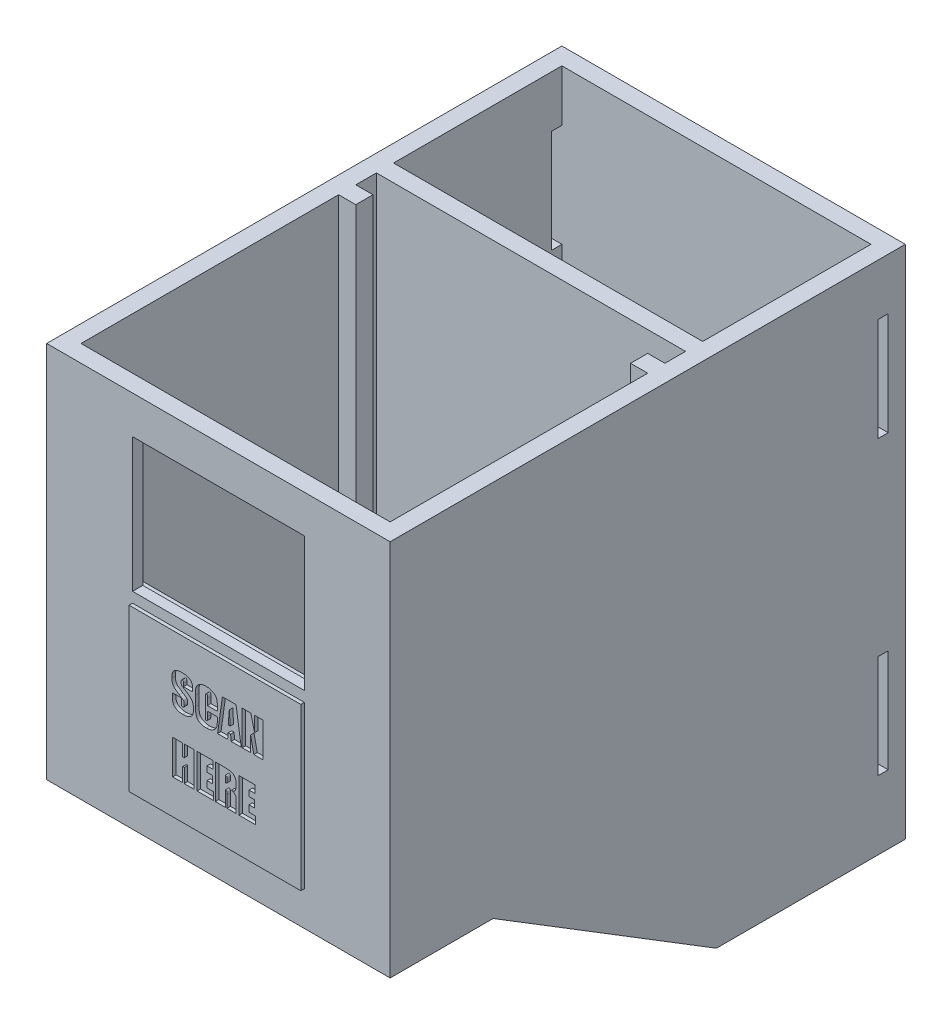
SolidWorks part; units mm, degrees
ref_plane "Front Plane" through (0, 0, 0) normal (0, 0, 1) x (1, 0, 0)
ref_plane "Top Plane" through (0, 0, 0) normal (0, 1, 0) x (1, 0, 0)
ref_plane "Right Plane" through (0, 0, 0) normal (1, 0, 0) x (0, 0, -1)
sketch "Sketch1" plane through (0, 0, 0) normal (0, 1, 0) x (1, 0, 0)
  line L1 (-50, -75) -> (50, -75)
  line L2 (-50, -75) -> (-50, 75)
  line L3 (-50, 75) -> (50, 75)
  line L4 (50, -75) -> (50, 75)
  line L5 (-50, -75) -> (50, 75) construction
  line L6 (-50, 75) -> (50, -75) construction
  point P0 (0, 0)
  dimension "D1" = 100
  dimension "D2" = 150
extrude "Boss-Extrude1" add sketch "Sketch1" along normal blind 150
sketch "Sketch13" plane through (50, 0, 0) normal (1, 0, 0) x (0, 0, -1)
  line L0 (-45, 40) -> (20, 0)
  line L1 (-75, 0) -> (-45, 0)
  line L2 (-75, 0) -> (-75, 40)
  line L3 (-75, 40) -> (-45, 40)
  line L5 (-75, 0) -> (75, 0) construction
  line L8 (-45, 0) -> (20, 0)
  dimension "D1" = 30
  dimension "D2" = 40
  dimension "D3" = 55
extrude "Cut-Extrude7" cut sketch "Sketch13" against normal up to next
shell "Shell1" thickness 5 removed face at (0, 150, 0)
sketch "Sketch3" plane through (0, 0, 0) normal (0, -1, 0) x (1, 0, 0)
  line L1 (50, 45) -> (50, 75) construction
  circle A0 centre (0, 60) radius 4
  circle A1 centre (-5, 50) radius 1.5
  circle A2 centre (5, 50) radius 1.5
  dimension "D3" = 8
  dimension "D4" = 3
  dimension "D5" = 10
  dimension "D7" = 10
  dimension "D8" = 5
  dimension "D1" = 60
  dimension "D2" = 50
extrude "Cut-Extrude2" cut sketch "Sketch3" against normal up to next
sketch "Sketch5" plane through (0, 0, 75) normal (0, 0, 1) x (1, 0, 0)
  line L0 (50, 150) -> (50, 40) construction
  line L1 (-25, 50) -> (25, 50)
  line L2 (-25, 50) -> (-25, 97)
  line L3 (-25, 97) -> (25, 97)
  line L4 (25, 50) -> (25, 97)
  line L5 (-25, 50) -> (25, 97) construction
  line L6 (-25, 97) -> (25, 50) construction
  line L7 (-50, 150) -> (50, 150) construction
  point P0 (0, 73.5)
  dimension "D1" = 50
  dimension "D2" = 47
  dimension "D3" = 50
  dimension "D4" = 76.5
extrude "Boss-Extrude3" add sketch "Sketch5" along normal blind 1
sketch "Sketch8" plane through (0, 0, 75) normal (0, 0, 1) x (1, 0, 0)
  line L0 (-50, 150) -> (-50, 40) construction
  line L1 (-25, 100) -> (25, 100)
  line L2 (-25, 100) -> (-25, 139)
  line L3 (-25, 139) -> (25, 139)
  line L4 (25, 100) -> (25, 139)
  line L5 (-25, 100) -> (25, 139) construction
  line L6 (-25, 139) -> (25, 100) construction
  line L7 (-50, 150) -> (50, 150) construction
  point P0 (0, 119.5)
  dimension "D1" = 50
  dimension "D2" = 39
  dimension "D3" = 50
  dimension "D4" = 50
extrude "Cut-Extrude3" cut sketch "Sketch8" against normal up to next
sketch "Sketch18" plane through (0, 0, 70) normal (0, 0, -1) x (-1, 0, 0)
  line L0 (-25, 139) -> (25, 139) construction
  line L1 (30, 99) -> (-26, 99)
  line L2 (30, 99) -> (30, 140)
  line L3 (30, 140) -> (-26, 140)
  line L4 (-26, 99) -> (-26, 140)
  line L6 (-25, 100) -> (-25, 139) construction
  line L7 (25, 139) -> (25, 100) construction
  dimension "D1" = 1
  dimension "D2" = 41
  dimension "D3" = 1
  dimension "D4" = 5
extrude "Cut-Extrude9" cut sketch "Sketch18" against normal blind 2
sketch "Sketch20" plane through (0, 0, 76) normal (0, 0, 1) x (1, 0, 0)
  line L0 (25, 97) -> (-25, 97) construction
  line L1 (-23, 96) -> (23, 96)
  line L2 (-23, 96) -> (-23, 51)
  line L3 (-23, 51) -> (23, 51)
  line L4 (23, 96) -> (23, 51)
  line L5 (-25, 50) -> (25, 50) construction
  line L6 (25, 50) -> (25, 97) construction
  line L7 (-25, 97) -> (-25, 50) construction
  dimension "D1" = 1
  dimension "D2" = 1
  dimension "D3" = 2
  dimension "D4" = 2
extrude "Cut-Extrude10" cut sketch "Sketch20" against normal blind 15 from offset 4 offset against normal yes
sketch "Sketch21" plane through (0, 45, 0) normal (0, 1, 0) x (1, 0, 0)
  line L1 (9, -52.5) -> (-9, -52.5)
  line L2 (9, -52.5) -> (9, -37.5)
  line L3 (9, -37.5) -> (-9, -37.5)
  line L4 (-9, -52.5) -> (-9, -37.5)
  circle A0 centre (5, -50) radius 1.5 construction
  circle A1 centre (-5, -50) radius 1.5 construction
  dimension "D3" = 4
  dimension "D1" = 4
  dimension "D2" = 2.5
  dimension "D4" = 15
extrude "Cut-Extrude11" cut sketch "Sketch21" against normal blind 2.5
sketch "Sketch22" plane through (-45, 0, 0) normal (1, 0, 0) x (0, 0, -1)
  line L0 (70, 150) -> (-70, 150) construction
  line L5 (70, 150) -> (70, 5) construction
  line L7 (-43.5848, 45) -> (21.4152, 5) construction
  line L8 (10, 150) -> (10, 12.0247)
  line L11 (10, 150) -> (5, 150)
  line L14 (5, 150) -> (5, 15.1017)
  line L15 (5, 15.1017) -> (10, 12.0247)
  dimension "D1" = 60
  dimension "D3" = 5
extrude "Boss-Extrude6" add sketch "Sketch22" along normal blind 5
mirror "Mirror2" about plane through (0, 0, 0) normal (1, 0, 0) of "Boss-Extrude6"
sketch "Sketch23" plane through (-45, 0, 0) normal (1, 0, 0) x (0, 0, -1)
  line L0 (16, 150) -> (21, 150)
  line L1 (70, 150) -> (10, 150) construction
  line L3 (21, 150) -> (21, 5.2555)
  line L4 (21, 5.2555) -> (16, 8.3324)
  line L6 (10, 12.0247) -> (10, 150) construction
  line L7 (16, 150) -> (16, 8.3324)
  line L8 (10, 12.0247) -> (21.4152, 5) construction
  dimension "D1" = 6
  dimension "D2" = 5
extrude "Boss-Extrude7" add sketch "Sketch23" along normal up to next
sketch "Sketch24" plane through (-45, 0, 0) normal (1, 0, 0) x (0, 0, -1)
  line L0 (70, 150) -> (70, 5) construction
  line L1 (70, 135) -> (67, 135)
  line L2 (70, 135) -> (70, 105)
  line L3 (70, 105) -> (67, 105)
  line L4 (67, 135) -> (67, 105)
  line L5 (70, 150) -> (21, 150) construction
  line L6 (70, 5) -> (21.4152, 5) construction
  line L7 (70, 20) -> (67, 20)
  line L8 (70, 20) -> (70, 50)
  line L9 (70, 50) -> (67, 50)
  line L10 (67, 20) -> (67, 50)
  dimension "D1" = 15
  dimension "D2" = 30
  dimension "D3" = 3
  dimension "D4" = 15
extrude "Cut-Extrude12" cut sketch "Sketch24" against normal through all both and the other way through all
sketch "Sketch28" plane through (0, 0, 76) normal (0, 0, 1) x (1, 0, 0)
  text T0 "SCAN\r\nHERE" font "Impact" height 10
extrude "Cut-Extrude14" cut sketch "Sketch28" against normal blind 1
sketch "Sketch30" plane through (0, 0, -75) normal (0, 0, -1) x (-1, 0, 0)
  text T0 "IBE VAN DE VEIRE\r\nSTEF GIELEN" font "Comic Sans MS" height 5
extrude "Cut-Extrude16" cut sketch "Sketch30" against normal blind 1
sketch "Sketch17" plane through (0, 8.927, -5.4936) normal (0, -0.8517, 0.5241) x (1, 0, 0)
  line L0 (-50, -17.0332) -> (50, -17.0332) construction
  line L1 (-10, 12.9668) -> (-12, 12.9668)
  line L2 (-12, 12.9668) -> (-12, 37.8867)
  line L3 (-10, 12.9668) -> (-8, 12.9668)
  line L4 (-8, 12.9668) -> (-8, 37.8867)
  line L5 (50, -17.0332) -> (50, 59.2885) construction
  line L6 (-11.4142, 11.5526) -> (-29.0352, 29.1736)
  line L7 (-8.5858, 14.381) -> (-26.2068, 32.0021)
  line L8 (-10, 12.9668) -> (-8.5858, 14.381)
  line L9 (-10, 10.9668) -> (-34.9199, 10.9668)
  line L10 (-10, 14.9668) -> (-34.9199, 14.9668)
  line L11 (-10, 12.9668) -> (-10, 14.9668)
  line L12 (-8.5858, 11.5526) -> (-26.2068, -6.0684)
  line L13 (-11.4142, 14.381) -> (-29.0352, -3.24)
  line L14 (-10, 12.9668) -> (-11.4142, 14.381)
  line L15 (-8, 12.9668) -> (-8, -11.953)
  line L16 (-12, 12.9668) -> (-12, -11.953)
  line L17 (-10, 12.9668) -> (-12, 12.9668)
  line L18 (-8.5858, 14.381) -> (9.0352, -3.24)
  line L19 (-11.4142, 11.5526) -> (6.2068, -6.0684)
  line L20 (-10, 12.9668) -> (-11.4142, 11.5526)
  line L21 (-10, 14.9668) -> (14.9199, 14.9668)
  line L22 (-10, 10.9668) -> (14.9199, 10.9668)
  line L23 (-10, 12.9668) -> (-10, 10.9668)
  line L24 (-11.4142, 14.381) -> (6.2068, 32.0021)
  line L25 (-8.5858, 11.5526) -> (9.0352, 29.1736)
  line L26 (-10, 12.9668) -> (-8.5858, 11.5526)
  circle A0 centre (-10, 12.9668) radius 25
  circle A1 centre (-10, 12.9668) radius 22.5
  circle A2 centre (-10, 12.9668) radius 20
  circle A3 centre (-10, 12.9668) radius 17.5
  circle A4 centre (-10, 12.9668) radius 5
  circle A5 centre (-10, 12.9668) radius 15
  circle A6 centre (-10, 12.9668) radius 12.5
  circle A7 centre (-10, 12.9668) radius 10
  circle A8 centre (-10, 12.9668) radius 7.5
  circle A9 centre (-10, 12.9668) radius 2.5
  dimension "D1" = 50
  dimension "D2" = 30
  dimension "D3" = 45
  dimension "D4" = 40
  dimension "D5" = 35
  dimension "D6" = 10
  dimension "D11" = 30
  dimension "D12" = 25
  dimension "D13" = 20
  dimension "D14" = 15
  dimension "D15" = 5
  dimension "D7" = 4
  dimension "D8" = 2
  dimension "D9" = 60
  dimension "D10" = 8
